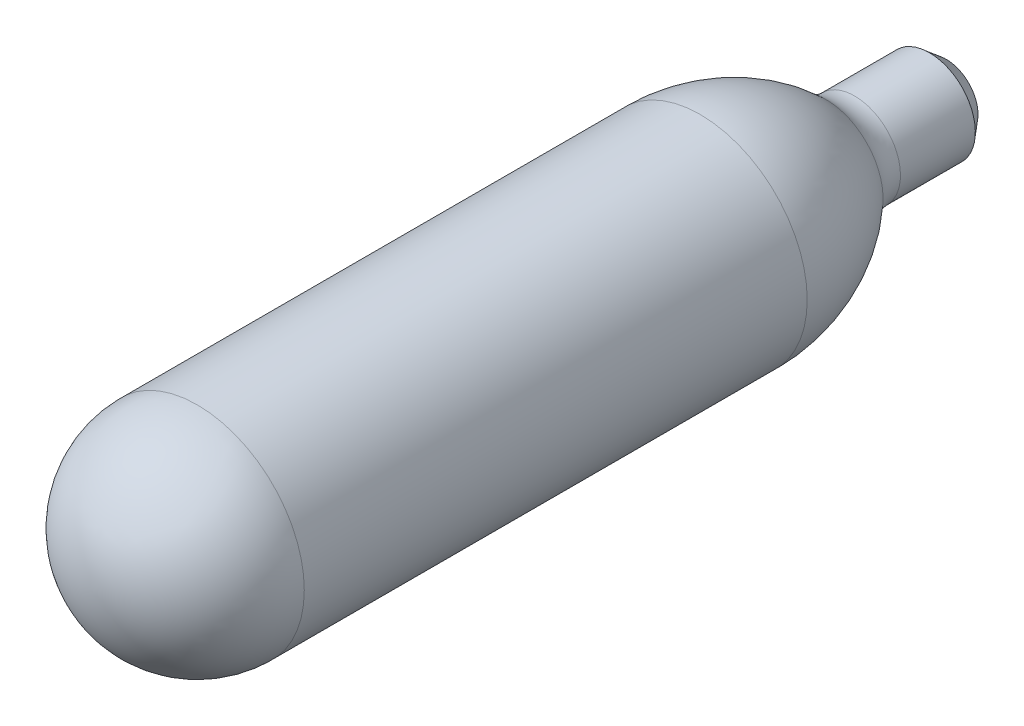
SolidWorks part; units mm, degrees
material "6061 Alloy"
ref_plane "Front Plane" through (0, 0, 0) normal (0, 0, 1) x (1, 0, 0)
ref_plane "Top Plane" through (0, 0, 0) normal (0, 1, 0) x (1, 0, 0)
ref_plane "Right Plane" through (0, 0, 0) normal (1, 0, 0) x (0, 0, -1)
sketch "Sketch3" plane through (0, 0, 0) normal (1, 0, 0) x (0, 0, -1)
  line L0 (40.9334, 9.1325) -> (48.7073, 9.1325)
  line L3 (-27.3291, 15.4825) -> (24.9016, 15.4825)
  line L4 (-38.4416, 4.37) -> (50.4584, 4.37)
  line L7 (48.7073, 9.1325) -> (50.4584, 7.6631)
  line L9 (50.4584, 4.37) -> (50.4584, 7.6631)
  arc A0 (-38.4416, 4.37) -> (-27.3291, 15.4825) centre (-27.3291, 4.37) cw
  arc A1 (37.9461, 10.3157) -> (24.9016, 15.4825) centre (24.9016, -3.5675) ccw
  arc A2 (37.9461, 10.3157) -> (40.9334, 9.1325) centre (40.9334, 13.4952) ccw
  dimension "D7" = 19.05
  dimension "D2" = 88.9
  dimension "D4" = 40
  dimension "D5" = 2.286
revolve "Revolve3" add sketch "Sketch3" angle 360 about L4
shell "Shell1" thickness 2.54
